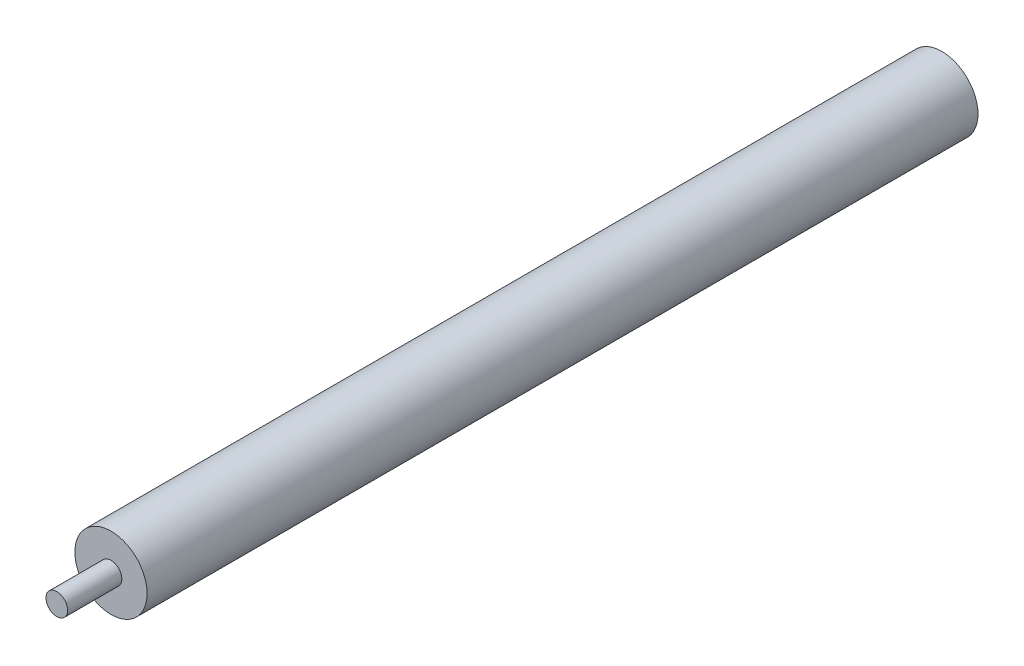
SolidWorks part; units mm, degrees
material "4032-T6"
ref_plane "Front Plane" through (0, 0, 0) normal (0, 0, 1) x (1, 0, 0)
ref_plane "Top Plane" through (0, 0, 0) normal (0, 1, 0) x (1, 0, 0)
ref_plane "Right Plane" through (0, 0, 0) normal (1, 0, 0) x (0, 0, -1)
sketch "Sketch1" plane through (0, 0, 0) normal (0, 0, 1) x (1, 0, 0)
  circle A0 centre (0, 0) radius 10
  dimension "D1" = 20
extrude "Boss-Extrude1" add sketch "Sketch1" along normal blind 230
sketch "Sketch2" plane through (0, 0, 230) normal (0, 0, 1) x (1, 0, 0)
  circle A0 centre (0, 0) radius 3
extrude "Boss-Extrude2" add sketch "Sketch2" along normal blind 15
